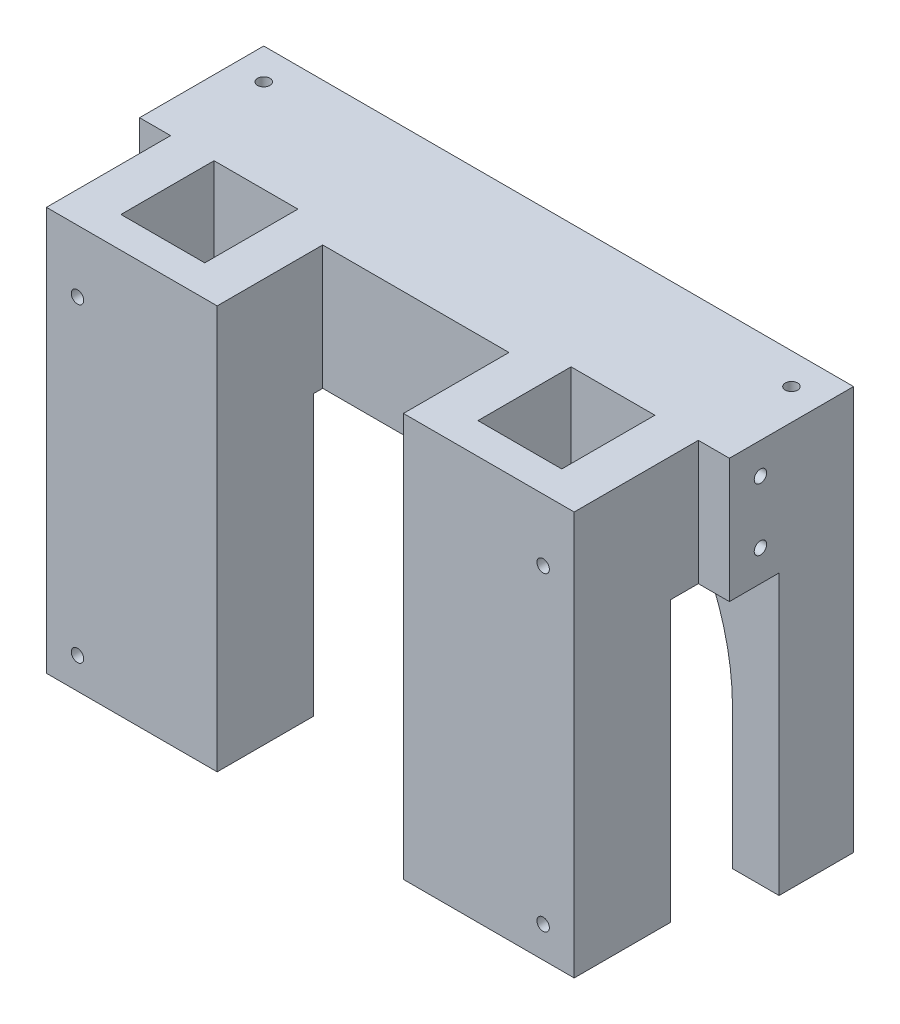
SolidWorks part; units mm, degrees
ref_plane "Plan de face" through (0, 0, 0) normal (0, 0, 1) x (1, 0, 0)
ref_plane "Plan de dessus" through (0, 0, 0) normal (0, 1, 0) x (1, 0, 0)
ref_plane "Plan de droite" through (0, 0, 0) normal (1, 0, 0) x (0, 0, -1)
sketch "Esquisse1" plane through (0, 0, 0) normal (0, 0, 1) x (1, 0, 0)
  line L1 (-47.5, 32.5) -> (47.5, 32.5)
  line L2 (-47.5, 32.5) -> (-47.5, -32.5)
  line L3 (-47.5, -32.5) -> (47.5, -32.5)
  line L4 (47.5, 32.5) -> (47.5, -32.5)
  point P4 (0, 32.5)
  point P5 (0, -32.5)
  point P6 (47.5, 0)
  point P7 (-47.5, 0)
  dimension "D1" = 95
  dimension "D2" = 65
extrude "Boss.-Extru.1" add sketch "Esquisse1" along normal blind 40
ref_plane "Plan1" through (0, -10, 0) normal (0, 1, 0) x (1, 0, 0)
sketch "Esquisse3" plane through (0, 0, 0) normal (0, 0, -1) x (-1, 0, 0)
  line L0 (22, -10) -> (-22, -10) construction
  circle A0 centre (0, -10) radius 40
  dimension "D1" = 80
extrude "Enlèv. mat.-Extru.1" cut sketch "Esquisse3" against normal blind 12
ref_plane "Plan2" through (-47.5, 32.5, 0) normal (0, 0, -1) x (-1, 0, 0)
sketch "Esquisse5" plane through (0, 32.5, 0) normal (0, 1, 0) x (1, 0, 0)
  line L1 (-42.5, -20) -> (-47.5, -20)
  line L2 (-42.5, -20) -> (-42.5, -40)
  line L3 (-42.5, -40) -> (-47.5, -40)
  line L4 (-47.5, -20) -> (-47.5, -40)
  dimension "D1" = 5
  dimension "D2" = 20
extrude "Enlèv. mat.-Extru.2" cut sketch "Esquisse5" against normal through all
sketch "Esquisse6" plane through (0, 32.5, 0) normal (0, 1, 0) x (1, 0, 0)
  line L0 (47.5, -40) -> (47.5, 0) construction
  line L1 (47.5, -20) -> (42.5, -20)
  line L2 (47.5, -20) -> (47.5, -40)
  line L3 (47.5, -40) -> (42.5, -40)
  line L4 (42.5, -20) -> (42.5, -40)
  line L5 (47.5, -40) -> (-42.5, -40) construction
  line L6 (-42.5, -20) -> (-47.5, -20) construction
  dimension "D1" = 5
extrude "Enlèv. mat.-Extru.3" cut sketch "Esquisse6" against normal through all
sketch "Esquisse7" plane through (0, 0, 0) normal (0, 0, -1) x (-1, 0, 0)
  line L0 (22, -10) -> (-22, -10) construction
  line L1 (-40, -10) -> (40, -10)
  line L2 (-40, -10) -> (-40, -32.5)
  line L3 (-40, -32.5) -> (40, -32.5)
  line L4 (40, -10) -> (40, -32.5)
  line L5 (47.5, -32.5) -> (33.0719, -32.5) construction
  arc A0 (33.0719, -32.5) -> (-33.0719, -32.5) centre (0, -10) ccw construction
  arc A1 (33.0719, -32.5) -> (-33.0719, -32.5) centre (0, -10) ccw construction
extrude "Enlèv. mat.-Extru.4" cut sketch "Esquisse7" against normal up to surface (12 mm away) up to face at (0, -1.25, 12)
sketch "Esquisse8" plane through (0, -32.5, 0) normal (0, -1, 0) x (1, 0, 0)
  line L0 (40, 12) -> (-40, 12) construction
  line L1 (-47.5, 24.5) -> (47.5, 24.5)
  line L2 (-47.5, 24.5) -> (-47.5, 12)
  line L3 (-47.5, 12) -> (47.5, 12)
  line L4 (47.5, 24.5) -> (47.5, 12)
  line L5 (-47.5, 20) -> (-47.5, 0) construction
  line L6 (47.5, 20) -> (47.5, 0) construction
  line L7 (-42.5, 40) -> (42.5, 40) construction
  dimension "D1" = 15.5
extrude "Enlèv. mat.-Extru.5" cut sketch "Esquisse8" against normal blind 45
sketch "Esquisse10" plane through (0, 0, 40) normal (0, 0, 1) x (1, 0, 0)
  line L0 (-42.5, -32.5) -> (42.5, -32.5) construction
  line L1 (-15, 32.5) -> (15, 32.5)
  line L2 (-15, 32.5) -> (-15, -32.5)
  line L3 (-15, -32.5) -> (15, -32.5)
  line L4 (15, 32.5) -> (15, -32.5)
  line L5 (42.5, 32.5) -> (-42.5, 32.5) construction
  point P6 (0, 32.5)
  dimension "D1" = 30
extrude "Enlèv. mat.-Extru.6" cut sketch "Esquisse10" against normal blind 17
sketch "Esquisse11" plane through (0, 32.5, 0) normal (0, 1, 0) x (1, 0, 0)
  line L0 (-15, -40) -> (-42.5, -40) construction
  line L1 (-35.5, -35) -> (-22, -35)
  line L2 (-35.5, -35) -> (-35.5, -20)
  line L3 (-35.5, -20) -> (-22, -20)
  line L4 (-22, -35) -> (-22, -20)
  line L5 (-42.5, -40) -> (-42.5, -20) construction
  line L6 (-15, -23) -> (-15, -40) construction
  line L10 (-42.5, -20) -> (-47.5, -20) construction
  dimension "D1" = 5
  dimension "D2" = 7
  dimension "D3" = 7
extrude "Enlèv. mat.-Extru.7" cut sketch "Esquisse11" against normal through all
sketch "Esquisse12" plane through (0, 32.5, 0) normal (0, 1, 0) x (1, 0, 0)
  line L0 (-35.5, -35) -> (-22, -35) construction
  line L1 (22, -20) -> (35.5, -20)
  line L2 (22, -20) -> (22, -35)
  line L3 (22, -35) -> (35.5, -35)
  line L4 (35.5, -20) -> (35.5, -35)
  line L5 (-22, -20) -> (-35.5, -20) construction
  line L6 (15, -23) -> (15, -40) construction
  line L7 (42.5, -20) -> (42.5, -40) construction
  dimension "D1" = 7
  dimension "D2" = 7
extrude "Enlèv. mat.-Extru.8" cut sketch "Esquisse12" against normal through all
sketch "Esquisse14" plane through (-47.5, 0, 0) normal (-1, 0, 0) x (0, 0, 1)
  line L0 (20, 12.5) -> (20, 32.5) construction
  line L2 (20, 32.5) -> (0, 32.5) construction
  circle A0 centre (15, 27.5) radius 1
  circle A1 centre (15, 17.5) radius 1
  dimension "D1" = 2
  dimension "D2" = 2
  dimension "D3" = 5
  dimension "D4" = 5
  dimension "D5" = 10
extrude "Enlèv. mat.-Extru.9" cut sketch "Esquisse14" against normal through all
sketch "Esquisse15" plane through (0, 0, 40) normal (0, 0, 1) x (1, 0, 0)
  line L0 (-15, 32.5) -> (-42.5, 32.5) construction
  line L2 (-42.5, -32.5) -> (-42.5, 32.5) construction
  line L3 (42.5, 12.5) -> (42.5, 32.5) construction
  line L4 (-42.5, -32.5) -> (-15, -32.5) construction
  circle A0 centre (-37.5, 22.5) radius 1
  circle A1 centre (37.5, 22.5) radius 1
  circle A2 centre (-37.5, -27.5) radius 1
  circle A3 centre (37.5, -27.5) radius 1
  dimension "D1" = 2
  dimension "D2" = 2
  dimension "D7" = 2
  dimension "D9" = 2
  dimension "D3" = 10
  dimension "D5" = 5
  dimension "D6" = 5
  dimension "D8" = 5
extrude "Enlèv. mat.-Extru.10" cut sketch "Esquisse15" against normal through all
sketch "Esquisse16" plane through (0, -32.5, 0) normal (0, -1, 0) x (1, 0, 0)
  line L0 (47.5, 12) -> (47.5, 0) construction
  line L1 (40, 0) -> (47.5, 0) construction
  line L2 (-47.5, 12) -> (-47.5, 0) construction
  circle A0 centre (42.5, 5) radius 1
  circle A1 centre (-42.5, 5) radius 1
  point P8 (-47.5, 6)
  dimension "D1" = 2
  dimension "D4" = 2
  dimension "D2" = 5
  dimension "D3" = 5
  dimension "D5" = 5
extrude "Enlèv. mat.-Extru.11" cut sketch "Esquisse16" against normal through all
